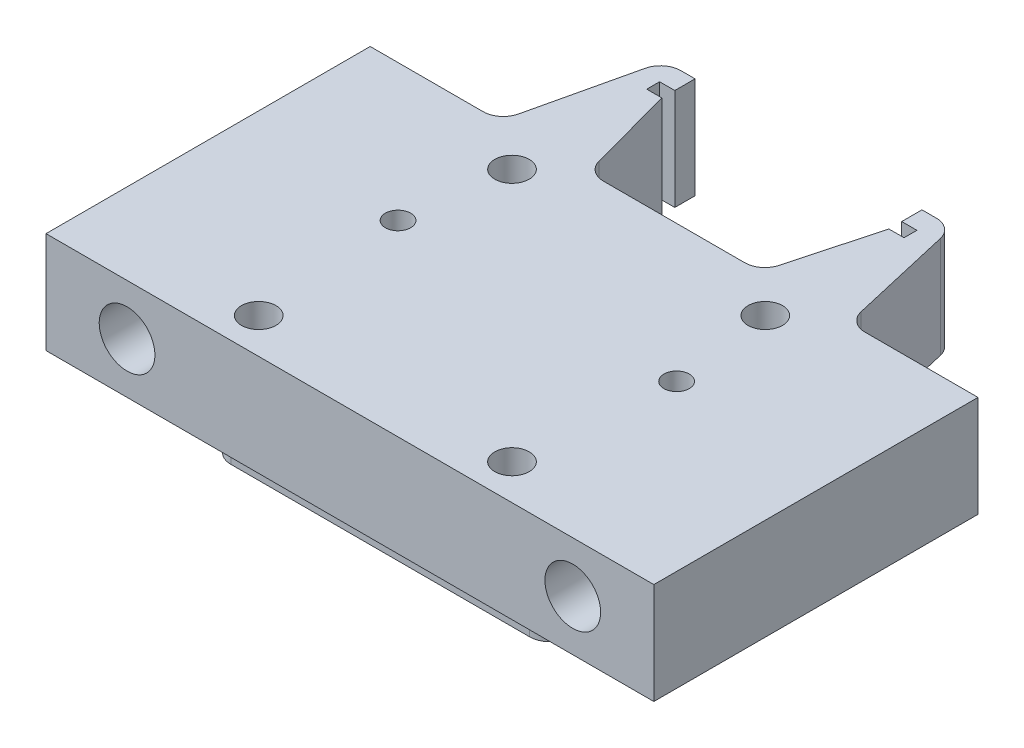
SolidWorks part; units mm, degrees
ref_plane "Front Plane" through (0, 0, 0) normal (0, 0, 1) x (1, 0, 0)
ref_plane "Top Plane" through (0, 0, 0) normal (0, 1, 0) x (1, 0, 0)
ref_plane "Right Plane" through (0, 0, 0) normal (1, 0, 0) x (0, 0, -1)
sketch "Sketch1" plane through (0, 0, 0) normal (0, 1, 0) x (1, 0, 0)
  line L1 (-12.5, 12.5) -> (12.5, 12.5)
  line L2 (-12.5, 12.5) -> (-12.5, -12.5)
  line L3 (-12.5, -12.5) -> (12.5, -12.5)
  line L4 (12.5, 12.5) -> (12.5, -12.5)
  line L5 (-12.5, 12.5) -> (12.5, -12.5) construction
  line L6 (-12.5, -12.5) -> (12.5, 12.5) construction
  line L7 (-30, 16) -> (30, 16)
  line L8 (-30, 16) -> (-30, -16)
  line L9 (-30, -16) -> (30, -16)
  line L10 (30, 16) -> (30, -16)
  line L11 (-30, 16) -> (30, -16) construction
  line L12 (-30, -16) -> (30, 16) construction
  point P0 (0, 0)
  point P6 (0, 0)
  dimension "D1" = 25
  dimension "D2" = 32
  dimension "D3" = 60
sketch "Sketch2" plane through (0, 0, 0) normal (0, 1, 0) x (1, 0, 0)
  line L0 (-30, 16) -> (30, 16) construction
  line L1 (30, 16) -> (30, -16) construction
  line L2 (-30, -16) -> (30, -16) construction
  line L3 (-30, 16) -> (-30, -16) construction
  line L4 (-30, 16) -> (30, 16)
  line L5 (30, 16) -> (30, -16)
  line L6 (-30, -16) -> (30, -16)
  line L7 (-30, 16) -> (-30, -16)
extrude "Boss-Extrude1" add sketch "Sketch2" along normal blind 10
hole_wizard "CBORE for M3 SHCS1" positions "Sketch3" profile "Sketch4" counterbore size "M3" standard "ANSI Metric" end condition through all
sketch "Sketch3" plane through (0, 0, 0) normal (0, -1, 0) x (-1, 0, 0)
  point P0 (12.5, 12.5)
  point P2 (12.5, -12.5)
  point P5 (-12.5, -12.5)
  point P8 (-12.5, 12.5)
  point P12 (12.5, 12.5)
sketch "Sketch4" plane through (-12.5, 0, -12.5) normal (1, 0, 0) x (0, 0, -1)
  line L0 (0, 0) -> (0, 10)
  line L1 (0, 10) -> (1.7, 10)
  line L3 (1.7, 10) -> (1.7, 5)
  line L4 (1.7, 5) -> (3.25, 5)
  line L5 (3.25, 5) -> (3.25, 0)
  line L7 (3.25, 0) -> (0, 0)
  line L11 (0, -6.35) -> (0, 107.95) construction
  dimension "Thru Hole Dia." = 3.4
  dimension "Thru Hole Depth" = 10
  dimension "C'Bore Dia." = 6.5
  dimension "C'Bore Depth" = 5
sketch "Sketch5" plane through (0, 0, 0) normal (0, -1, 0) x (1, 0, 0)
  line L1 (10.5, -12) -> (-10.5, -12)
  line L2 (10.5, -12) -> (10.5, 1)
  line L3 (10.5, 12) -> (-10.5, 12)
  line L4 (-10.5, -12) -> (-10.5, 1)
  line L5 (10.5, -12) -> (-10.5, 12) construction
  line L6 (10.5, 12) -> (-10.5, -12) construction
  line L7 (10.5, 1) -> (12.5, 1)
  line L8 (12.5, 1) -> (12.5, 7)
  line L9 (12.5, 7) -> (10.5, 7)
  line L10 (10.5, 7) -> (10.5, 12)
  line L11 (-10.5, 7) -> (-10.5, 12)
  line L12 (-10.5, 1) -> (-12.5, 1)
  line L14 (-10.5, 7) -> (-12.5, 7)
  line L15 (-12.5, 1) -> (-12.5, 7)
  point P0 (0, 0)
  dimension "D1" = 24
  dimension "D2" = 21
  dimension "D3" = 5
  dimension "D4" = 6
  dimension "D5" = 2
extrude "Cut-Extrude1" cut sketch "Sketch5" against normal blind 3
sketch "Sketch6" plane through (0, 0, 0) normal (0, -1, 0) x (-1, 0, 0)
  line L0 (9.2887, 12) -> (-9.2887, 12) construction
  line L1 (8.5, 12) -> (-8.5, 12)
  line L2 (8.5, 12) -> (8.5, 16)
  line L3 (8.5, 16) -> (-8.5, 16)
  line L4 (-8.5, 12) -> (-8.5, 16)
  line L5 (30, 16) -> (-30, 16) construction
  line L6 (0, 0) -> (0, 12) construction
  dimension "D1" = 17
extrude "Cut-Extrude2" cut sketch "Sketch6" against normal blind 2
sketch "Sketch7" plane through (0, 0, 0) normal (0, -1, 0) x (1, 0, 0)
  line L0 (9.2887, 12) -> (-9.2887, 12) construction
  line L1 (-12.5, -12.5) -> (-12.5, 12.5) construction
  line L2 (12.5, -12.5) -> (12.5, 12.5) construction
  line L3 (-13.75, -2.5) -> (13.75, -2.5) construction
  circle A0 centre (-13.75, -2.5) radius 1.25
  circle A2 centre (13.75, -2.5) radius 1.25
  dimension "D2" = 2.5
  dimension "D1" = 14.5
extrude "Cut-Extrude3" cut sketch "Sketch7" against normal through all
chamfer "Chamfer1" distance 0.5 angle 40 2 edges at (-13.75, 0, -3.75) (13.75, 0, -3.75) first distance on face at (-13.75, 0, -3.75)
sketch "Sketch8" plane through (0, 0, -16) normal (0, 0, -1) x (-1, 0, 0)
  line L0 (30, 5) -> (-30, 5) construction
  line L1 (30, 10) -> (30, 0) construction
  line L2 (-30, 10) -> (-30, 0) construction
  line L4 (17.2657, 5) -> (19.6329, 0.9)
  line L5 (19.6329, 0.9) -> (24.3671, 0.9)
  line L6 (24.3671, 0.9) -> (26.7343, 5)
  line L7 (26.7343, 5) -> (24.3671, 9.1)
  line L8 (24.3671, 9.1) -> (19.6329, 9.1)
  line L9 (19.6329, 9.1) -> (17.2657, 5)
  line L10 (-17.2657, 5) -> (-19.6329, 9.1)
  line L11 (-19.6329, 9.1) -> (-24.3671, 9.1)
  line L12 (-24.3671, 9.1) -> (-26.7343, 5)
  line L13 (-26.7343, 5) -> (-24.3671, 0.9)
  line L14 (-24.3671, 0.9) -> (-19.6329, 0.9)
  line L15 (-19.6329, 0.9) -> (-17.2657, 5)
  circle A0 centre (22, 5) radius 4.1 construction
  circle A1 centre (-22, 5) radius 4.1 construction
  point P15 (-20.7193, 9.5578)
  dimension "D1" = 8.2
  dimension "D2" = 8
  dimension "D3" = 8
extrude "Cut-Extrude4" cut sketch "Sketch8" against normal blind 5
hole_wizard "M5 Clearance Hole1" positions "Sketch10" profile "Sketch11" hole size "M5" standard "ANSI Metric" end condition through all
sketch "Sketch10" plane through (0, 0, -11) normal (0, 0, -1) x (-1, 0, 0)
  line L0 (19.6329, 0.9) -> (24.3671, 9.1)
  line L2 (-19.6329, 9.1) -> (-24.3671, 0.9)
  point P0 (22, 5)
  point P2 (-22, 5)
  point P16 (0, 0)
sketch "Sketch11" plane through (-22, 5, -11) normal (1, 0, 0) x (0, 1, 0)
  line L0 (0, 0) -> (0, 27)
  line L1 (0, 27) -> (2.75, 27)
  line L2 (2.75, 27) -> (2.75, 0)
  line L5 (2.75, 0) -> (0, 0)
  line L11 (0, -6.35) -> (0, 107.95) construction
  dimension "Thru Hole Dia." = 5.5
  dimension "Thru Hole Depth" = 27
sketch "Sketch15" plane through (0, 0, 0) normal (0, -1, 0) x (1, 0, 0)
  line L0 (9.2887, 12) -> (-9.2887, 12) construction
  line L1 (11.75, -10) -> (-11.75, -10)
  line L2 (11.75, -10) -> (11.75, -4.7361)
  line L3 (11.75, 10) -> (-11.75, 10)
  line L4 (-11.75, -10) -> (-11.75, -4.7361)
  line L5 (11.75, -10) -> (-11.75, 10) construction
  line L6 (11.75, 10) -> (-11.75, -10) construction
  line L7 (8.5, -12) -> (9.2887, -12) construction
  line L8 (16.75, -13) -> (-16.75, -13)
  line L9 (16.75, -13) -> (16.75, 13)
  line L10 (16.75, 13) -> (-16.75, 13)
  line L11 (-16.75, -13) -> (-16.75, 13)
  line L12 (16.75, -13) -> (-16.75, 13) construction
  line L13 (16.75, 13) -> (-16.75, -13) construction
  line L14 (11.75, -0.2639) -> (11.75, 10)
  line L15 (-11.75, -0.2639) -> (-11.75, 10)
  circle A0 centre (-13.75, -2.5) radius 1.25 construction
  circle A1 centre (13.75, -2.5) radius 1.6
  circle A2 centre (-13.75, -2.5) radius 1.6
  arc A3 (11.75, -4.7361) -> (11.75, -0.2639) centre (13.75, -2.5) cw
  arc A4 (-11.75, -0.2639) -> (-11.75, -4.7361) centre (-13.75, -2.5) cw
  point P0 (0, 0)
  point P10 (0, 0)
  dimension "D5" = 3.2
  dimension "D6" = 3
  dimension "D1" = 2
  dimension "D2" = 2
  dimension "D3" = 3
  dimension "D4" = 1
extrude "Boss-Extrude3" add sketch "Sketch15" along normal blind 3 from offset 0.6 separate body
fillet "Fillet1" radius 2 10 edges at (-16.75, -2.1, 13) (16.75, -2.1, 13) (16.75, -2.1, -13) (-16.75, -2.1, -13) (-11.75, -2.1, -10) (-11.75, -2.1, 10) (11.75, -2.1, 10) (11.75, -2.1, -0.2639) (11.75, -2.1, -4.7361) (11.75, -2.1, -10)
sketch "Sketch16" plane through (0, 0, 0) normal (0, -1, 0) x (1, 0, 0)
  line L0 (0, 0) -> (0, -29.7145) construction
  line L1 (-12.7, -16) -> (-12.7, -26) construction
  line L2 (-8.5, -16) -> (-30, -16) construction
  line L3 (-17.2657, -16) -> (-12.7, -16)
  line L4 (-17.2657, -16) -> (-14.2, -29.27)
  line L5 (-14.2, -29.27) -> (-11.2, -29.27)
  line L6 (-11.2, -29.27) -> (-11.2, -27.27)
  line L7 (-11.2, -27.27) -> (-12.7, -27.27)
  line L8 (-12.7, -27.27) -> (-12.7, -26)
  line L9 (-12.7, -26) -> (-11.2, -26)
  line L11 (-11.2, -26) -> (-8.5, -16)
  line L12 (-8.5, -16) -> (-12.7, -16)
  point P4 (-11.2, -25.1446)
  point P14 (0, 0)
  point P15 (-13.99, -29.27)
  point P18 (-12.7, -30.8913)
  point P20 (-11.2, -26.0953)
  point P21 (-9.0792, -26)
  dimension "D1" = 12.7
  dimension "D2" = 1.5
  dimension "D3" = 10
  dimension "D4" = 1.27
  dimension "D5" = 2
  dimension "D6" = 3
extrude "Boss-Extrude4" add sketch "Sketch16" against normal up to surface (10 mm away) up to face at (-13.75, 10, -3.75)
fillet "Fillet2" radius 2 4 edges at (-8.5, 6, -16) (-14.2, 5, -29.27) (-17.2657, 2.5, -16) (-17.2657, 7.5, -16)
mirror "Mirror1" about plane through (0, 0, 0) normal (1, 0, 0) of "Fillet2", "Boss-Extrude4"
